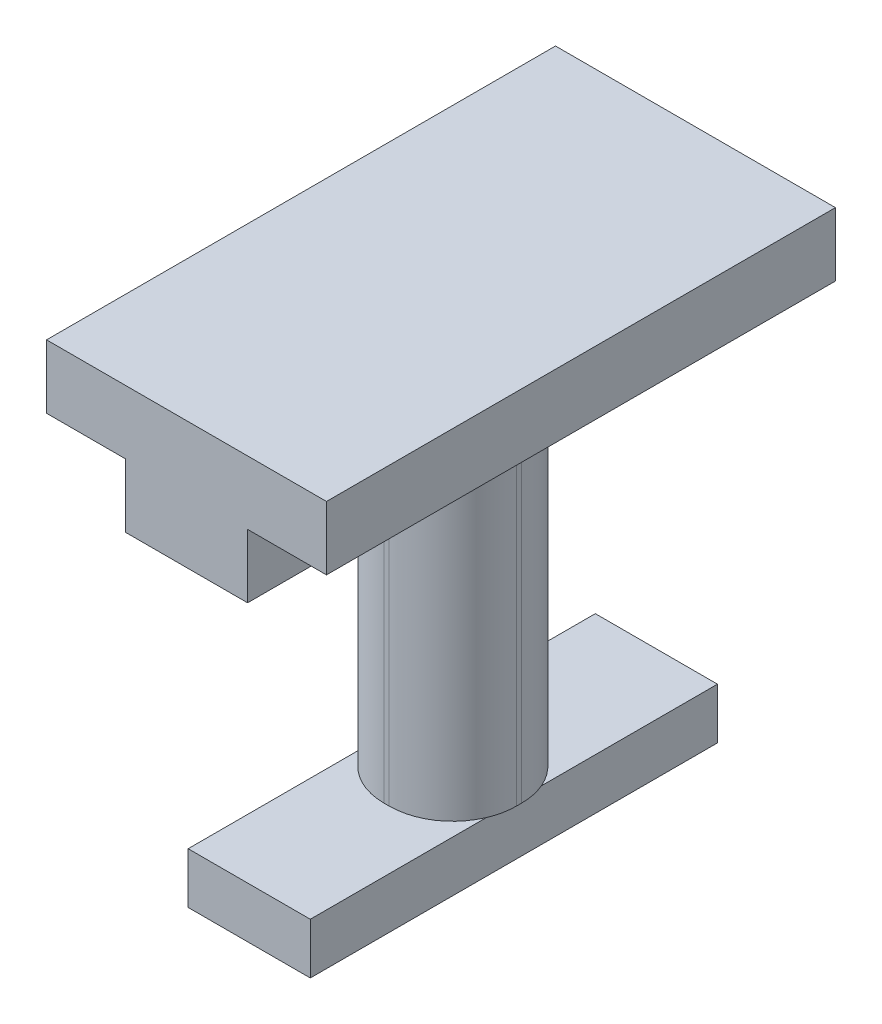
SolidWorks part; units mm, degrees
ref_plane "Alzado" through (0, 0, 0) normal (0, 0, 1) x (1, 0, 0)
ref_plane "Planta" through (0, 0, 0) normal (0, 1, 0) x (1, 0, 0)
ref_plane "Vista lateral" through (0, 0, 0) normal (1, 0, 0) x (0, 0, -1)
sketch "Croquis1" plane through (0, 0, 0) normal (0, 0, 1) x (1, 0, 0)
  line L0 (-5.5, 0) -> (5.5, 0)
  line L1 (5.5, 0) -> (5.5, -2.5)
  line L2 (5.5, -2.5) -> (2.4, -2.5)
  line L3 (2.4, -2.5) -> (2.4, -5)
  line L4 (2.4, -5) -> (-2.4, -5)
  line L5 (0, 0) -> (0, -5) construction
  line L6 (-2.4, -2.5) -> (-2.4, -5)
  line L7 (-5.5, -2.5) -> (-2.4, -2.5)
  line L8 (-5.5, 0) -> (-5.5, -2.5)
  dimension "D1" = 5.5
  dimension "D2" = 2.5
  dimension "D3" = 2.5
  dimension "D4" = 3.1
extrude "Saliente-Extruir1" add sketch "Croquis1" along normal blind 20
sketch "Croquis2" plane through (0, -5, 0) normal (0, -1, 0) x (1, 0, 0)
  line L2 (-2.6, 6.9359) -> (2.6, 6.9359)
  line L3 (-2.6, 6.9359) -> (-2.6, 12.1359)
  line L4 (2.6, 6.9359) -> (2.6, 12.1359)
  line L5 (-2.6, 12.1359) -> (2.6, 12.1359)
  line L6 (-2.6, 6.9359) -> (2.6, 12.1359) construction
  line L7 (2.6, 6.9359) -> (-2.6, 12.1359) construction
  point P0 (0, 0)
  dimension "D1" = 5.2
  dimension "D2" = 5.2
extrude "Saliente-Extruir2" add sketch "Croquis2" along normal blind 12
sketch "Croquis3" plane through (0, -17, 0) normal (0, -1, 0) x (1, 0, 0)
  line L0 (2.4, 17.5359) -> (-2.4, 17.5359)
  line L1 (2.4, 6.9359) -> (2.4, 0) construction
  line L2 (-2.4, 20) -> (-2.4, 12.1359) construction
  line L3 (2.4, 20) -> (2.4, 0) construction
  line L4 (2.4, 1.5359) -> (2.4, 17.5359)
  line L5 (-2.4, 17.5359) -> (-2.4, 1.5359)
  line L6 (-2.4, 20) -> (-2.4, 0) construction
  line L7 (-2.4, 1.5359) -> (2.4, 1.5359)
  dimension "D1" = 16
extrude "Saliente-Extruir4" add sketch "Croquis3" along normal blind 2
fillet "Redondeo4" radius 2.5 4 edges at (-2.6, -11, 12.1359) (-2.6, -11, 6.9359) (2.6, -11, 12.1359) (2.6, -11, 6.9359)
